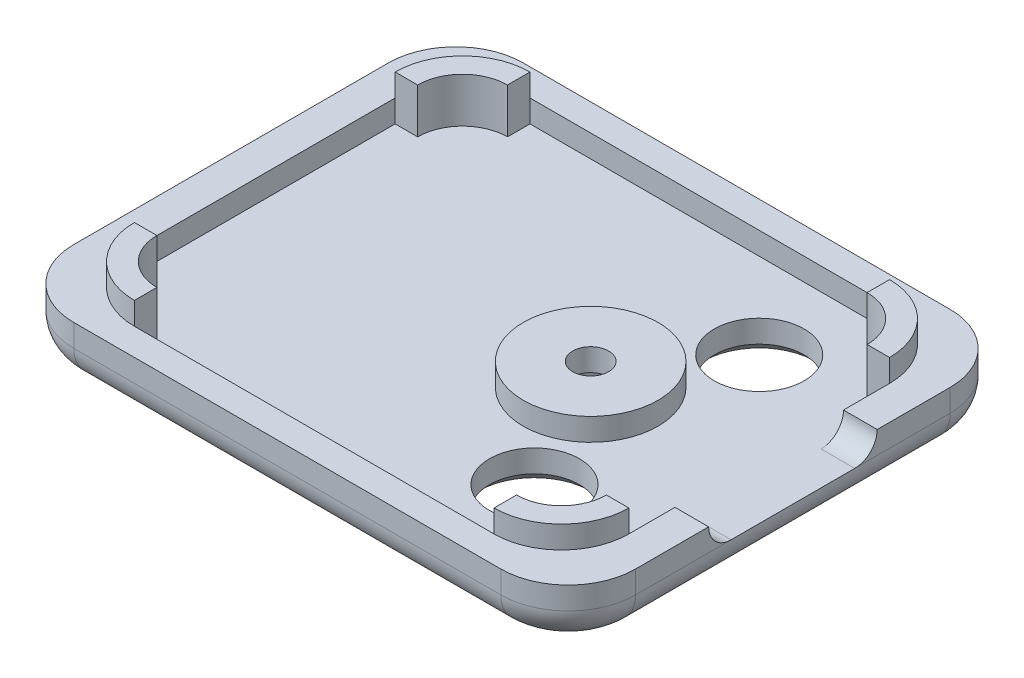
SolidWorks part; units mm, degrees
ref_plane "Front Plane" through (0, 0, 0) normal (0, 0, 1) x (1, 0, 0)
ref_plane "Top Plane" through (0, 0, 0) normal (0, 1, 0) x (1, 0, 0)
ref_plane "Right Plane" through (0, 0, 0) normal (1, 0, 0) x (0, 0, -1)
sketch "Sketch1" plane through (0, 0, 0) normal (0, 1, 0) x (1, 0, 0)
  line L1 (25, -20) -> (-25, -20)
  line L2 (25, -20) -> (25, 20)
  line L3 (25, 20) -> (-25, 20)
  line L4 (-25, -20) -> (-25, 20)
  line L5 (25, -20) -> (-25, 20) construction
  line L6 (25, 20) -> (-25, -20) construction
  line L7 (-22, -17.6) -> (22, -17.6)
  line L8 (-22, -17.6) -> (-22, 17.6)
  line L9 (-22, 17.6) -> (22, 17.6)
  line L10 (22, -17.6) -> (22, 17.6)
  line L11 (-22, -17.6) -> (22, 17.6) construction
  line L12 (-22, 17.6) -> (22, -17.6) construction
  point P0 (0, 0)
  point P6 (0, 0)
  dimension "D1" = 50
  dimension "D2" = 40
  dimension "D3" = 44
extrude "Boss-Extrude1" add sketch "Sketch1" along normal blind 5
sketch "Sketch2" plane through (0, 0, 0) normal (0, -1, 0) x (-1, 0, 0)
  line L1 (22, 17.6) -> (-22, 17.6)
  line L2 (22, 17.6) -> (22, -17.6)
  line L3 (22, -17.6) -> (-22, -17.6)
  line L4 (-22, 17.6) -> (-22, -17.6)
  line L5 (22, 17.6) -> (-22, -17.6) construction
  line L6 (22, -17.6) -> (-22, 17.6) construction
  point P0 (0, 0)
extrude "Boss-Extrude2" add sketch "Sketch2" against normal blind 3
sketch "Sketch3" plane through (0, 3, 0) normal (0, 1, 0) x (1, 0, 0)
  line L0 (25, -20) -> (25, 20) construction
  circle A0 centre (7, 0) radius 6
  dimension "D1" = 12
  dimension "D2" = 18
extrude "Boss-Extrude3" add sketch "Sketch3" along normal up to surface (2 mm away) up to face at (0, 5, 0)
sketch "Sketch4" plane through (0, 5, 0) normal (0, 1, 0) x (1, 0, 0)
  circle A0 centre (7, 0) radius 1.6
  dimension "D1" = 3.2
extrude "Cut-Extrude1" cut sketch "Sketch4" against normal up to surface (5 mm away) up to face at (0, 0, 0)
fillet "Fillet1" radius 6 8 edges at (-25, 2.5, -20) (-25, 2.5, 20) (25, 2.5, 20) (25, 2.5, -20) (-22, 4, -17.6) (-22, 4, 17.6) (22, 4, 17.6) (22, 4, -17.6)
fillet "Fillet2" radius 3 8 edges at (-23.2426, 0, -18.2426) (0, 0, -20) (23.2426, 0, -18.2426) (25, 0, 0) (23.2426, 0, 18.2426) (0, 0, 20) (-23.2426, 0, 18.2426) (-25, 0, 0)
sketch "Sketch6" plane through (0, 0, 0) normal (0, -1, 0) x (-1, 0, 0)
  line L1 (-3.75, 0) -> (-5.375, 2.8146)
  line L2 (-5.375, 2.8146) -> (-8.625, 2.8146)
  line L3 (-8.625, 2.8146) -> (-10.25, 0)
  line L4 (-10.25, 0) -> (-8.625, -2.8146)
  line L5 (-8.625, -2.8146) -> (-5.375, -2.8146)
  line L6 (-5.375, -2.8146) -> (-3.75, 0)
  circle A0 centre (-7, 0) radius 2.8146 construction
  dimension "D1" = 3.25
extrude "Cut-Extrude2" cut sketch "Sketch6" against normal blind 3
sketch "Sketch8" plane through (0, 0, 0) normal (0, -1, 0) x (-1, 0, 0)
  line L1 (-19, -17) -> (19, -17) construction
  line L2 (-22, 14) -> (-22, -14) construction
  line L3 (19, 17) -> (-19, 17) construction
  circle A0 centre (-12, -10) radius 4
  circle A1 centre (-12, 10) radius 4
  dimension "D5" = 8
  dimension "D6" = 8
  dimension "D1" = 7
  dimension "D2" = 10
  dimension "D3" = 7
  dimension "D4" = 10
extrude "Cut-Extrude3" cut sketch "Sketch8" against normal up to surface (3 mm away) up to face at (7, 3, 6)
chamfer "Chamfer1" distance 1 angle 45 2 edges at (12, 0, -14) (12, 0, 6)
sketch "Sketch9" plane through (0, 5, 0) normal (0, 1, 0) x (1, 0, 0)
  line L0 (25, -14) -> (25, 14) construction
  line L1 (25, -7.5) -> (22, -7.5)
  line L2 (25, -7.5) -> (25, 7.5)
  line L3 (25, 7.5) -> (22, 7.5)
  line L4 (22, -7.5) -> (22, 7.5)
  line L5 (22, -11.6) -> (22, 11.6) construction
  circle A0 centre (7, 0) radius 1.6 construction
  dimension "D1" = 15
  dimension "D2" = 7.5
extrude "Cut-Extrude4" cut sketch "Sketch9" against normal blind 2
fillet "Fillet3" radius 2 2 edges at (23.5, 3, -7.5) (23.5, 3, 7.5)
sketch "Sketch10" plane through (0, 3, 0) normal (0, 1, 0) x (1, 0, 0)
  line L0 (-16, -17.6) -> (-16, -11.6)
  line L1 (-16, -11.6) -> (-22, -11.6)
  line L2 (-16, 17.6) -> (-16, 11.6)
  line L3 (-16, 11.6) -> (-22, 11.6)
  line L4 (16, 17.6) -> (16, 11.6)
  line L5 (16, 11.6) -> (22, 11.6)
  line L6 (22, -11.6) -> (16, -11.6)
  line L7 (16, -11.6) -> (16, -17.6)
  arc A0 (-16, -17.6) -> (-22, -11.6) centre (-16, -11.6) cw
  arc A1 (-22, -11.6) -> (-16, -17.6) centre (-16, -11.6) ccw construction
  arc A2 (-16, 17.6) -> (-22, 11.6) centre (-16, 11.6) ccw
  arc A3 (-16, 17.6) -> (-22, 11.6) centre (-16, 11.6) ccw construction
  arc A4 (22, 11.6) -> (16, 17.6) centre (16, 11.6) ccw
  arc A5 (22, -11.6) -> (16, -17.6) centre (16, -11.6) cw
  arc A6 (16, -17.6) -> (22, -11.6) centre (16, -11.6) ccw construction
extrude "Boss-Extrude5" add sketch "Sketch10" along normal blind 4
sketch "Sketch11" plane through (0, 7, 0) normal (0, 1, 0) x (1, 0, 0)
  line L0 (-16, -11.6) -> (-22, -11.6) construction
  circle A0 centre (16, 11.6) radius 4
  circle A1 centre (16, -11.6) radius 4
  circle A2 centre (-16, -11.6) radius 4
  circle A3 centre (-16, 11.6) radius 4
extrude "Cut-Extrude5" cut sketch "Sketch11" against normal up to surface (4 mm away) up to face at (12, 3, 14)
